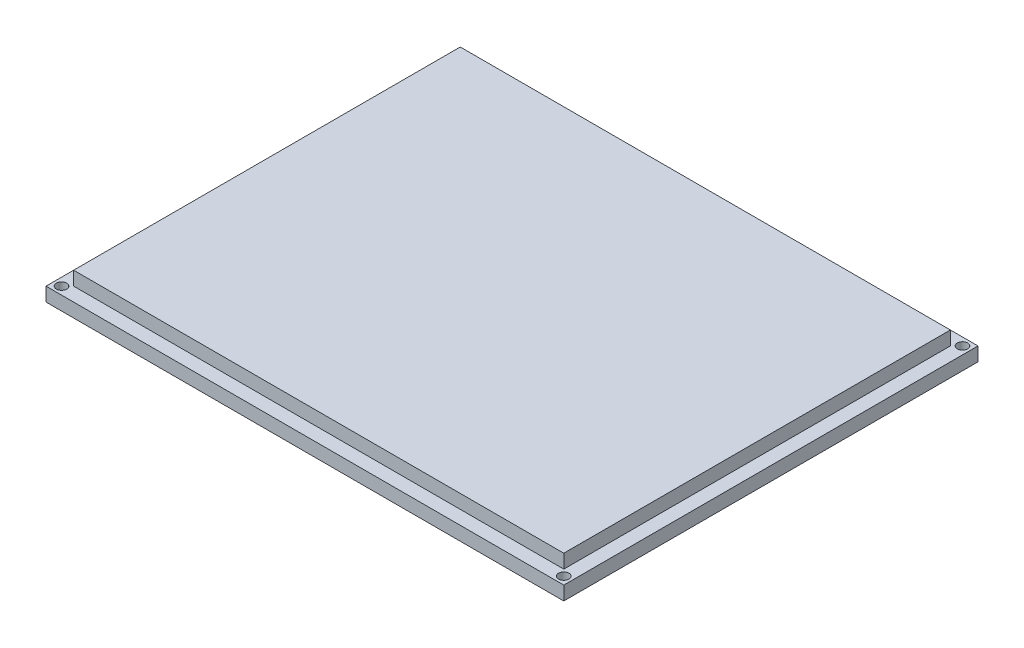
SolidWorks part; units mm, degrees
other "Markup1"
sketch "Sketch5" plane through (-105, 0, 60.5) normal (-0.0451, -0.9984, 0.0353) x (-0.7444, 0.01, -0.6676)
other "Markup2"
sketch "Sketch6" plane through (97, 11, -60) normal (0.0014, 0.7787, -0.6274) x (0.9996, 0.0165, 0.0227)
ref_plane "Front Plane" through (0, 0, 0) normal (0, 0, 1) x (1, 0, 0)
ref_plane "Top Plane" through (0, 0, 0) normal (0, 1, 0) x (1, 0, 0)
ref_plane "Right Plane" through (0, 0, 0) normal (1, 0, 0) x (0, 0, -1)
sketch "Sketch1" plane through (0, 0, 0) normal (0, 1, 0) x (1, 0, 0)
  line L1 (-105, 60) -> (45, 60)
  line L2 (-105, 60) -> (-105, -60)
  line L3 (-105, -60) -> (45, -60)
  line L4 (45, 60) -> (45, -60)
  dimension "D1" = 120
  dimension "D2" = 150
  dimension "D3" = 105
  dimension "D4" = 60
extrude "Top" add sketch "Sketch1" along normal blind 4
sketch "Sketch2" plane through (0, 4, 0) normal (0, 1, 0) x (1, 0, 0)
  line L1 (-101, -56) -> (41, -56)
  line L2 (-101, -56) -> (-101, 56)
  line L3 (-101, 56) -> (41, 56)
  line L4 (41, -56) -> (41, 56)
  dimension "D1" = 112
  dimension "D2" = 142
  dimension "D3" = 101
  dimension "D4" = 56
extrude "Bottom" add sketch "Sketch2" along normal blind 4
sketch "Sketch4" plane through (0, 4, 0) normal (0, 1, 0) x (1, 0, 0)
  line L0 (-105, 60) -> (-105, -60) construction
  line L1 (-105, -60) -> (45, -60) construction
  circle A0 centre (-102.75, -57.75) radius 1.5
  dimension "D1" = 2.25
  dimension "D3" = 3
  dimension "D2" = 2.25
extrude "Hole" cut sketch "Sketch4" against normal up to next
pattern_linear "Hole-Pattern" count 2 spacing 115.5 along (0, 0, -1) count 2 spacing 145.5 along (1, 0, 0) of "Hole"
